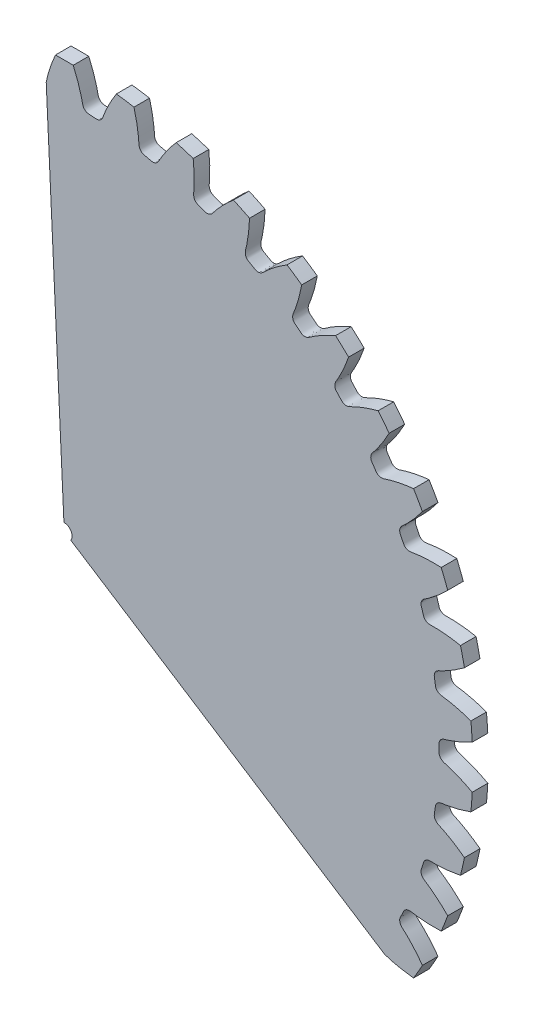
SolidWorks part; units mm, degrees
ref_plane "Front Plane" through (0, 0, 0) normal (0, 0, 1) x (1, 0, 0)
ref_plane "Top Plane" through (0, 0, 0) normal (0, 1, 0) x (1, 0, 0)
ref_plane "Right Plane" through (0, 0, 0) normal (1, 0, 0) x (0, 0, -1)
ref_axis "Axis1" through (0, 0, 55) along (0, 0, -1)
sketch "SketchRevolveGeartrax1Pinion" plane through (0, 0, 0) normal (1, 0, 0) x (0, 0, -1)
  line L0 (0, 0) -> (1, 0) construction
  line L1 (-4, 0) -> (-4, 209.9802)
  line L2 (-4, 209.9802) -> (4, 209.9802)
  line L3 (4, 209.9802) -> (4, 0)
  line L4 (4, 0) -> (-4, 0)
  dimension "Side1" = 4
  dimension "OutsideRadius" = 209.9802
  dimension "Side2" = 4
revolve "Geartrax1Pinion" add sketch "SketchRevolveGeartrax1Pinion" angle 360 about L0
sketch "SketchToothGeartrax1Pinion" plane through (0, 0, 0) normal (0, 0, 1) x (1, 0, 0)
  arc A0 (210.0599, 11.334) -> (210.0599, -11.334) centre (0, 0) cw
  spline S0 degree 3 poles (210.0599, -11.334) (209.4217, -10.9881) (208.4711, -10.4875) (207.2086, -9.8529) (206.2955, -9.408) (205.4033, -8.9869) (204.5325, -8.589) (203.6837, -8.2138) (202.8572, -7.8607) (202.0533, -7.529) (201.2727, -7.2181) (200.5155, -6.9274) (199.7822, -6.6563) (199.0732, -6.404) (198.3887, -6.1702) (197.7293, -5.9536) (197.0948, -5.7551) (196.207, -5.483) (195.4417, -5.3001) (194.8373, -5.0557) (194.6186, -4.9551) (194.3918, -4.8357) (194.154, -4.6908) (193.9022, -4.5108) (193.6355, -4.2818) (193.3577, -3.9861) (193.0818, -3.6032) (192.8378, -3.1183) (192.6687, -2.5501) (192.5961, -1.4951) (192.6776, 0) (192.5961, 1.4951) (192.6687, 2.5501) (192.8378, 3.1183) (193.0818, 3.6032) (193.3577, 3.9861) (193.6355, 4.2818) (193.9022, 4.5108) (194.154, 4.6908) (194.3918, 4.8357) (194.6186, 4.9551) (194.8373, 5.0557) (195.4417, 5.3001) (196.207, 5.483) (197.0948, 5.7551) (197.7293, 5.9536) (198.3887, 6.1702) (199.0732, 6.404) (199.7822, 6.6563) (200.5155, 6.9274) (201.2727, 7.2181) (202.0533, 7.529) (202.8572, 7.8607) (203.6837, 8.2138) (204.5325, 8.589) (205.4033, 8.9869) (206.2955, 9.408) (207.2086, 9.8529) (208.4711, 10.4875) (209.4217, 10.9881) (210.0599, 11.334) knots 0 0 0 0 0.04842 0.071654 0.094238 0.116172 0.137455 0.158088 0.178071 0.197403 0.216085 0.234117 0.251499 0.26823 0.284311 0.299741 0.314521 0.328651 0.361696 0.366792 0.372106 0.377751 0.383874 0.390667 0.398374 0.40728 0.417674 0.429733 0.443337 0.456892 0.5 0.543108 0.556663 0.570267 0.582326 0.59272 0.601626 0.609333 0.616126 0.622249 0.627894 0.633208 0.638304 0.671349 0.685479 0.700259 0.715689 0.73177 0.748501 0.765883 0.783915 0.802597 0.821929 0.841912 0.862545 0.883828 0.905762 0.928346 0.95158 1 1 1 1
extrude "ToothExtrudeCutGeartrax1Pinion" cut sketch "SketchToothGeartrax1Pinion" against normal blind 4 and the other way blind 4
pattern_circular "PatternGeartrax1Pinion" count 42 every 8.571 about axis through (0, 0, 55) along (0, 0, -1) of "ToothExtrudeCutGeartrax1Pinion"
sketch "BoreRevolveSketch" plane through (0, 0, 0) normal (1, 0, 0) x (0, 0, -1)
  line L0 (0, 0) -> (1, 0) construction
  line L1 (-4, 0) -> (4, 0)
  line L2 (4, 0) -> (4, 4)
  line L3 (4, 4) -> (-4, 4)
  line L4 (-4, 4) -> (-4, 0)
  dimension "BoreSide1" = 4
  dimension "TaperSide1" = 4
  dimension "BoreSide2" = 4
  dimension "TaperSide2" = 4
revolve "BoreRevolveCut" cut sketch "BoreRevolveSketch" angle 360 about L0
sketch "AuxiliarySketchGeartrax1Pinion" plane through (0, 0, 0) normal (0, 0, 1) x (1, 0, 0)
  circle A0 centre (0, 0) radius 202.2745 construction
  circle A1 centre (0, 0) radius 190.0759 construction
  circle A2 centre (0, 0) radius 195.6998 construction
  circle A3 centre (0, 0) radius 209.9802 construction
  circle A4 centre (0, 0) radius 192.6424 construction
  dimension "PitchDiameter" = 404.549
  dimension "BaseDiameter" = 380.1517
  dimension "FormDiameter" = 391.3995
  dimension "MajorDiameter" = 419.9604
  dimension "MinorDiameter" = 385.2848
sketch "Sketch1" plane through (0, 0, 4) normal (0, 0, 1) x (1, 0, 0)
  line L0 (0, 0) -> (-9.9808, 209.7429)
  line L1 (0, 0) -> (176.6523, -113.515)
  arc A1 (176.6523, -113.515) -> (-9.9808, 209.7429) centre (0, 0) ccw
  circle A4 centre (0, 0) radius 209.9802 construction
  point P1 (0, 0)
  point P3 (0, 0)
  point P5 (0, 0)
  point P9 (0, 0)
  point P11 (0, 0)
  point P13 (0, 0)
  dimension "D2" = 9.9808
  dimension "D1" = 125.449
extrude "Cut-Extrude1" cut sketch "Sketch1" against normal through all flip side to cut
